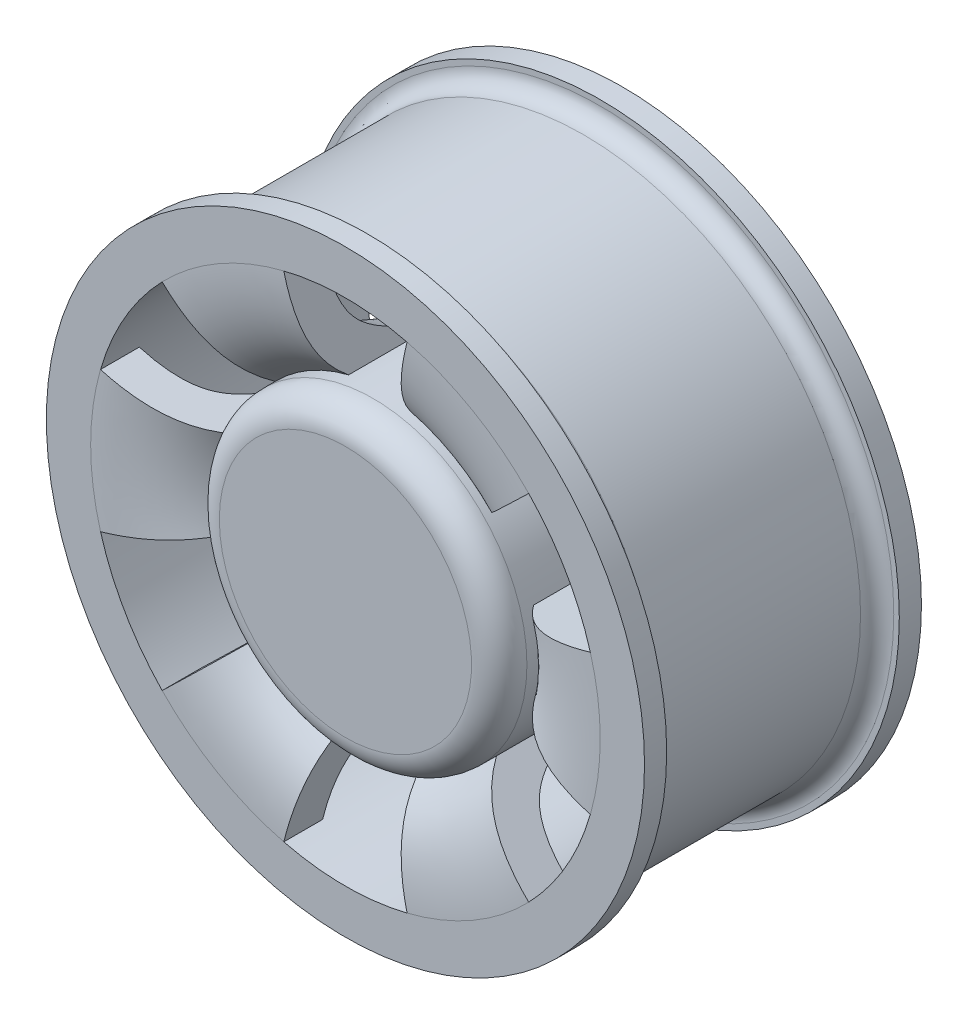
SolidWorks part; units mm, degrees
material "2024 Сплав"
ref_plane "Спереди" through (0, 0, 0) normal (0, 0, 1) x (1, 0, 0)
ref_plane "Сверху" through (0, 0, 0) normal (0, 1, 0) x (1, 0, 0)
ref_plane "Справа" through (0, 0, 0) normal (1, 0, 0) x (0, 0, -1)
sketch "Эскиз1" plane through (0, 0, 0) normal (0, 1, 0) x (1, 0, 0)
  line L0 (0, 0) -> (0, 47.4199) construction
  line L1 (0, 0) -> (79.812, 0) construction
  line L2 (46, 25) -> (46, -18)
  line L3 (46, -25) -> (54, -25)
  line L4 (54, -25) -> (54, -21)
  line L5 (54, -21) -> (53, -21)
  line L6 (50, -18) -> (50, 18)
  line L7 (54, 21) -> (53, 21)
  line L8 (54, 25) -> (54, 21)
  line L9 (46, 25) -> (54, 25)
  line L10 (40.0579, -25) -> (51.9421, -25) construction
  line L11 (20.5, 0) -> (27.7696, 0)
  arc A0 (53, -21) -> (50, -18) centre (53, -18) cw
  arc A1 (53, 21) -> (50, 18) centre (53, 18) ccw
  spline S0 degree 3 poles (46, -25) (27.8278, -25) (24.5333, -14.4961) (20.5, 0) knots 0 0 0 0 1 1 1 1
  spline S1 degree 1 poles (46, -18) (27.2438, 1.8764) knots 0 0 1 1 construction
  spline S2 degree 3 poles (46, -18) (45.5342, -18) (44.5772, -17.9825) (42.8692, -17.8825) (40.9712, -17.6453) (39.0897, -17.2169) (37.0322, -16.4976) (35.1527, -15.3982) (33.3638, -13.658) (31.6998, -11.1302) (30.4075, -8.2385) (29.4243, -5.4874) (28.7027, -3.2226) (28.1026, -1.1773) (27.6171, 0.5373) (27.3672, 1.4331) (27.2438, 1.8764) knots 0 0 0 0 0.03125 0.0625 0.125 0.1875 0.25 0.375 0.5 0.625 0.75 0.8125 0.875 0.9375 0.96875 1 1 1 1 only from (46, -18) to (27.7696, 0)
  point P3 (50, 21)
  point P12 (50, -21)
  point P16 (50, 0)
  point P19 (46, 0)
  dimension "D5" = 3
  dimension "D1" = 25
  dimension "D2" = 8
  dimension "D3" = 4
  dimension "D4" = 4
  dimension "D6" = 50
  dimension "D7" = 20.5
  dimension "D8" = 28
  dimension "D10" = 18
  dimension "D11" = 7.2696
  dimension "D9" = 7
revolve "Повернуть1" add sketch "Эскиз1" angle 360 about L0
sketch "Эскиз2" plane through (0, 0, 0) normal (0, 0, -1) x (-1, 0, 0)
  circle A0 centre (0, 0) radius 20.5 construction
  circle A1 centre (0, 0) radius 27.7695 construction
  circle A2 centre (0, 0) radius 20.5
  circle A3 centre (0, 0) radius 27.7695
extrude "Бобышка-Вытянуть1" add sketch "Эскиз2" against normal through all
sketch "Эскиз3" plane through (0, 0, 25) normal (0, 0, 1) x (1, 0, 0)
  circle A0 centre (0, 0) radius 27.7695 construction
  circle A1 centre (0, 0) radius 27.7695
extrude "Бобышка-Вытянуть2" add sketch "Эскиз3" against normal blind 5
sketch "Эскиз4" plane through (0, 0, 25) normal (0, 0, 1) x (1, 0, 0)
  line L0 (-6.7181, 26.9447) -> (-11.1284, 44.6336)
  line L1 (6.7181, 26.9447) -> (11.1284, 44.6336)
  circle A0 centre (0, 0) radius 27.7695 construction
  arc A1 (6.7181, 26.9447) -> (-6.7181, 26.9447) centre (0, 0) ccw
  circle A2 centre (0, 0) radius 46 construction
  arc A3 (11.1284, 44.6336) -> (-11.1284, 44.6336) centre (0, 0) ccw
  dimension "D1" = 28
extrude "Вырез-Вытянуть1" cut sketch "Эскиз4" against normal through all
pattern_circular "Круговой массив1" count 6 over 360 about axis through (0, 0, 25) along (0, 0, -1) of "Вырез-Вытянуть1"
fillet "Скругление1" radius 5 1 edges at (-27.7695, 0, 25)
sketch3d "Трехмерный эскиз1"
  line L0 (0, 0, 0) -> (-27.7695, 0, 0) construction
  arc A0 (-26.6938, 7.6543, 0) -> (-26.6938, -7.6543, 0) centre (0, 0, 0) ccw construction
  point P6 (0, 0, 27.7696)
  point P7 (-23.75, 0, 0)
  dimension "D1" = 23.75
hole_wizard "Сверление под метчик M51" positions "Эскиз11" profile "Эскиз13" hole size "M5" standard "ISO"
sketch "Эскиз11" plane through (0, 0, 0) normal (0, 0, -1) x (-1, 0, 0)
  point P0 (23.75, 0)
sketch "Эскиз13" plane through (-23.75, 0, 0) normal (1, 0, 0) x (0, 1, 0)
  line L0 (0, 0) -> (0, 23.2618)
  line L1 (0, 23.2618) -> (2.1, 22)
  line L2 (2.1, 22) -> (2.1, 0)
  line L5 (2.1, 0) -> (0, 0)
  line L10 (0, 23.2618) -> (-2.1, 22) construction
  line L11 (0, -6.35) -> (0, 107.95) construction
  dimension "Диаметр отверстия" = 4.2
  dimension "Глубина отверстия" = 22
  dimension "Угол заточки сверла" = 118
cosmetic thread "Условное изображение резьбы1" parameters "D2"=5
pattern_circular "Круговой массив3" count 6 over 360 about axis through (0, 0, 25) along (0, 0, -1) of "Сверление под метчик M51" reverse direction yes
chamfer "Фаска2" distance 0.6 angle 45 6 edges at (-13.975, -20.5681, 0) (9.775, -20.5681, 0) (21.65, 0, 0) (9.775, 20.5681, 0) (-13.975, 20.5681, 0) (-25.85, 0, 0)
